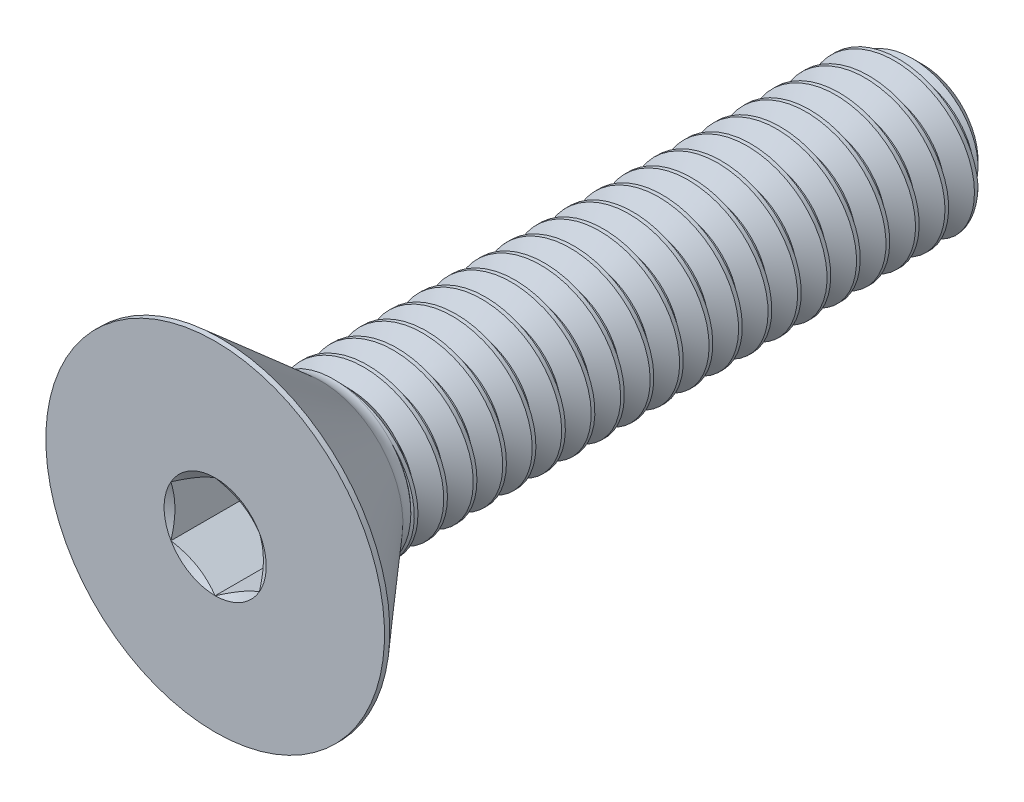
SolidWorks part; units mm, degrees
material "Cast Alloy Steel"
ref_plane "Front" through (0, 0, 0) normal (0, 0, 1) x (1, 0, 0)
ref_plane "Top" through (0, 0, 0) normal (0, 1, 0) x (1, 0, 0)
ref_plane "Right" through (0, 0, 0) normal (1, 0, 0) x (0, 0, -1)
sketch "Sketch1" plane through (0, 0, 0) normal (1, 0, 0) x (0, 0, -1)
  line L0 (0, 4.5593) -> (0.1422, 4.5593) construction
  line L1 (0.1422, 4.5593) -> (2.8448, 2.21) construction
  line L2 (0, 2.0828) -> (19.05, 2.0828)
  line L3 (19.05, 2.0828) -> (19.05, 0)
  line L4 (19.05, 0) -> (0, 0)
  line L5 (0, 0) -> (0, 4.5593) construction
  line L6 (0, 4.5593) -> (0, -4.5593) construction
  line L7 (19.05, 2.0828) -> (19.05, -2.0828) construction
  line L8 (0, -4.5593) -> (0.1422, -4.5593) construction
  line L9 (0.1422, -4.5593) -> (2.8448, -2.21) construction
  line L11 (0, 2.0828) -> (0, 0)
  line L12 (3.185, 2.0828) -> (3.185, 0) construction
  line L13 (-6.35, 0) -> (-6.35, 2.0828) construction
  arc A1 (2.8448, 2.21) -> (3.185, 2.0828) centre (3.185, 2.6014) ccw construction
  dimension "D1" = 0.1422
  dimension "Head Ht" = 2.8448
  dimension "Head Dia" = 9.1186
  dimension "Dia" = 4.1656
  dimension "Lg" = 19.05
  dimension "Head Angle" = 82
  dimension "Min Thread" = 25.4
revolve "Revolve1" add sketch "Sketch1" angle 360 mid plane about L4
sketch "Sketch3" plane through (0, 0, -19.05) normal (0, 0, -1) x (-1, 0, 0)
  circle A0 centre (0, 0) radius 2.0828
curve "Helix/Spiral1" pitch 0.7937 height 19.05 turns 24
sketch "Sketch2" plane through (0, 0, 0) normal (1, 0, 0) x (0, 0, -1)
  line L0 (19.05, 2.0828) -> (19.7445, 2.0828)
  line L1 (19.7445, 2.0828) -> (19.4469, 1.5672)
  line L2 (19.4469, 1.5672) -> (19.3477, 1.5672)
  line L3 (19.3477, 1.5672) -> (19.05, 2.0828)
  line L4 (19.1988, 1.825) -> (19.5957, 1.825) construction
  dimension "D1" = 60
  dimension "D2" = 0.0992
  dimension "D3" = 0.3969
ref_plane "Plane2" through (0, 0, 6.35) normal (0, 0, 1) x (1, 0, 0)
chamfer "Chamfer1" distance 0.5953 angle 45 1 edges at (0, 2.0828, -19.05)
sweep "Cut-Sweep1" cut profiles "Sketch2" path "Helix/Spiral1"
sketch "Sketch7" plane through (0, 0, 0) normal (1, 0, 0) x (0, 0, -1)
  line L0 (0, 4.5593) -> (0.1422, 4.5593) construction
  line L1 (0.1422, 4.5593) -> (2.8448, 2.21) construction
  line L2 (0, 4.5593) -> (0.1422, 4.5593)
  line L3 (0.1422, 4.5593) -> (2.8448, 2.21)
  line L4 (3.185, 2.0828) -> (3.185, 0) construction
  line L5 (3.185, 2.0828) -> (3.185, 0)
  line L7 (0, 0) -> (0, 4.5593) construction
  line L8 (0, 0) -> (0, 4.5593)
  line L9 (0, 0) -> (3.185, 0)
  line L10 (5.7417, 0) -> (-5.7417, 0) construction
  arc A0 (2.8448, 2.21) -> (3.185, 2.0828) centre (3.185, 2.6014) ccw construction
  arc A1 (2.8448, 2.21) -> (3.185, 2.0828) centre (3.185, 2.6014) ccw
revolve "Revolve2" add sketch "Sketch7" angle 360 mid plane about L9
ref_plane "Plane1" through (0, 0, -3.185) normal (0, 0, 1) x (1, 0, 0)
sketch "Sketch8" plane through (0, 0, -3.185) normal (0, 0, 1) x (1, 0, 0)
  circle A0 centre (0, 0) radius 2.0828
extrude "Boss-Extrude1" add sketch "Sketch8" against normal through all draft 46
sketch "Sketch5" plane through (0, 0, 0) normal (0, 0, 1) x (1, 0, 0)
  line L0 (0, 0) -> (-1.3748, 0) construction
  line L1 (0, 0) -> (-2.7496, 1.5875) construction
  line L2 (0, 0) -> (-2.7496, -1.5875) construction
  line L6 (0, 1.3748) -> (0, 1.1339) construction
  line L7 (0, 1.1339) -> (0, 0.893) construction
  line L9 (0, 1.3748) -> (-1.1906, 0.6874)
  line L10 (-1.1906, 0.6874) -> (-1.1906, -0.6874)
  line L11 (-1.1906, -0.6874) -> (0, -1.3748)
  line L12 (0, -1.3748) -> (1.1906, -0.6874)
  line L13 (1.1906, -0.6874) -> (1.1906, 0.6874)
  line L14 (1.1906, 0.6874) -> (0, 1.3748)
  circle A0 centre (0, 0) radius 1.3748 construction
  circle A1 centre (0, 0) radius 1.1339 construction
  circle A2 centre (0, 0) radius 0.893 construction
  circle A3 centre (0, 0) radius 1.1906 construction
  dimension "D3" = 1.7859
  dimension "Hex" = 2.3813
  dimension "D4" = 30
  dimension "D5" = 30
extrude "Cut-Extrude2" cut sketch "Sketch5" against normal blind 1.9914
sketch "Sketch6" plane through (0, 0, 0) normal (0, 0, 1) x (1, 0, 0)
  circle A0 centre (0, 0) radius 1.3748
extrude "Cut-Extrude3" cut sketch "Sketch6" against normal blind 1.9914 draft 60
sketch "Sketch9" [suppressed] plane through (0, 0, -3.6076) normal (0, 0, 1) x (1, 0, 0)
  circle A1 centre (0, 0) radius 2.413
  circle A2 centre (0, 0) radius 2.413
  point P0 (0, 2.413)
  dimension "D1" = 0
extrude "Boss-Extrude2" [suppressed] add sketch "Sketch9" against normal up to surface (15.4424 mm away)
sketch "Sketch10" plane through (0, 0, 0) normal (1, 0, 0) x (0, 0, -1)
  line L0 (19.05, 2.0828) -> (19.05, -2.0828) construction
  point P0 (17.8594, -2.0828)
  dimension "D1" = 1.1906
equation "\"D3@Helix/Spiral1\" = \"Lg@Sketch1\""
equation "\"D2@Sketch2\" = \"D4@Helix/Spiral1\" * .125"
equation "\"D3@Sketch2\" = \"D4@Helix/Spiral1\" * .5"
equation "\"D1@Chamfer1\" = \"D4@Helix/Spiral1\" * .75"
equation "\"D1@Cut-Extrude2\" = \"Head Ht@Sketch1\" * .7"
equation "\"D1@Sketch1\" = \"Head Ht@Sketch1\" * .05"
equation "\"D1@Sketch10\" = \"D4@Helix/Spiral1\" * 1.5"
equation "\"D1@Cut-Extrude3\" = \"D1@Cut-Extrude2\""
equation "\"D3@Sketch5\" = \"Hex@Sketch5\" * .75"
